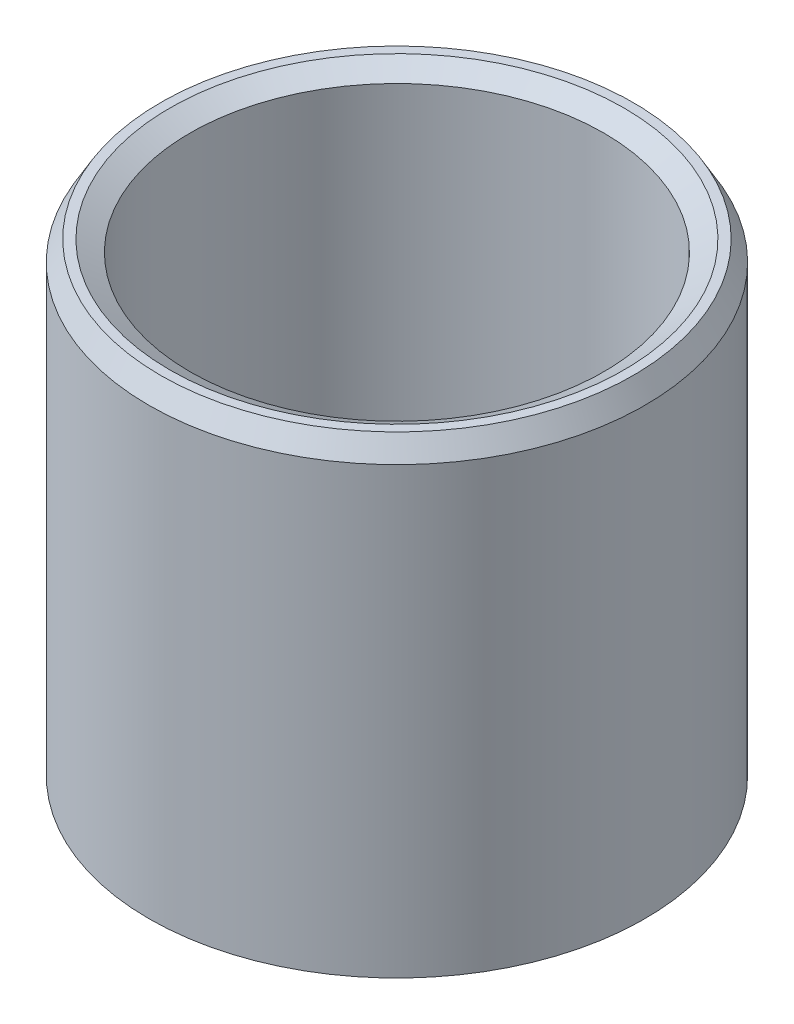
SolidWorks part; units mm, degrees
ref_plane "Front Plane" through (0, 0, 0) normal (0, 0, 1) x (1, 0, 0)
ref_plane "Top Plane" through (0, 0, 0) normal (0, 1, 0) x (1, 0, 0)
ref_plane "Right Plane" through (0, 0, 0) normal (1, 0, 0) x (0, 0, -1)
sketch "Sketch1" plane through (0, 0, 0) normal (0, 1, 0) x (1, 0, 0)
  circle A0 centre (0, 0) radius 42.5
  dimension "SLEEVE_OD" = 85
extrude "Boss-Extrude1" add sketch "Sketch1" along normal blind 81.6454
sketch "Sketch2" plane through (0, 0, 0) normal (0, 1, 0) x (1, 0, 0)
  circle A0 centre (0, 0) radius 35.4566
  dimension "BORE_D" = 70.9132
extrude "Cut-Extrude1" cut sketch "Sketch2" along normal through all
chamfer "Chamfer1" distance 3.4493 angle 30 4 edges at (0, 81.6454, 35.4566) (0, 0, 35.4566) (0, 0, 42.5) (0, 81.6454, 42.5) first distance on face at (0, 81.6454, 35.4566) first distance on face at (0, 0, 35.4566) first distance on face at (0, 81.6454, 42.5)
